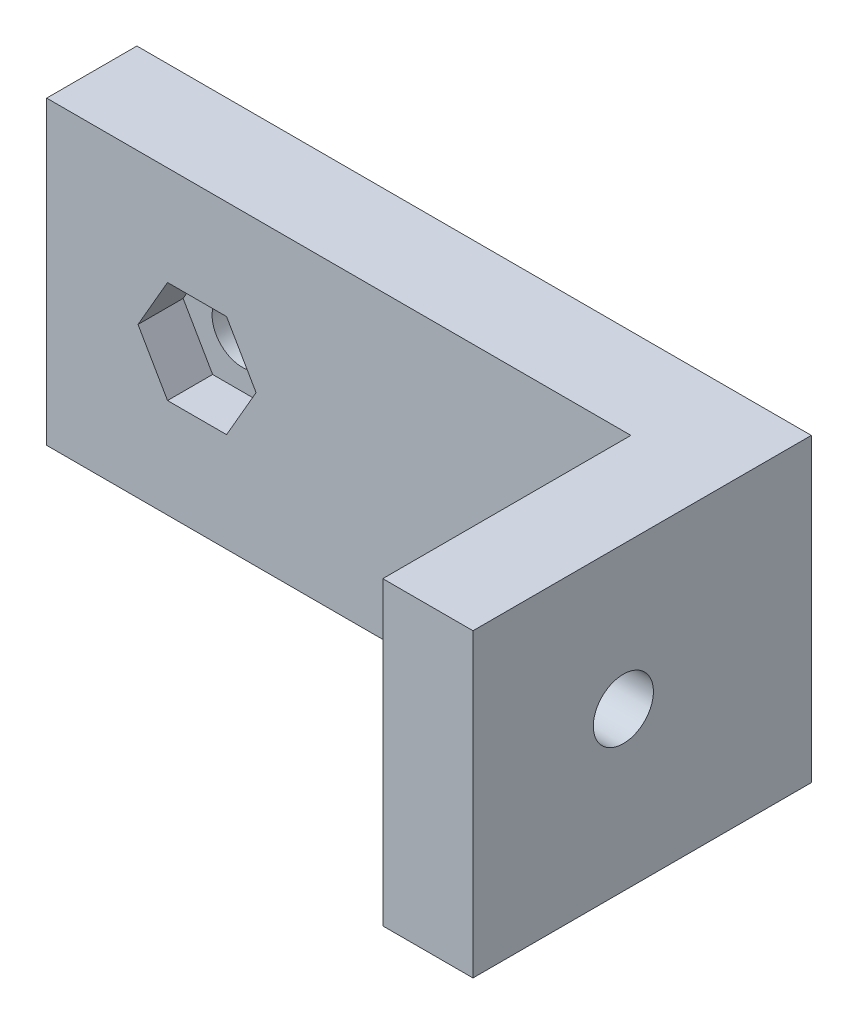
SolidWorks part; units mm, degrees
material "ABS"
ref_plane "Front Plane" through (0, 0, 0) normal (0, 0, 1) x (1, 0, 0)
ref_plane "Top Plane" through (0, 0, 0) normal (0, 1, 0) x (1, 0, 0)
ref_plane "Right Plane" through (0, 0, 0) normal (1, 0, 0) x (0, 0, -1)
sketch "Sketch1" plane through (0, 0, 0) normal (0, 0, 1) x (1, 0, 0)
  line L0 (169.7, 102.9317) -> (169.7, 86.2) construction
  line L1 (169.7, -7.5) -> (124.85, -7.5)
  line L2 (169.7, -7.5) -> (169.7, 12.5)
  line L3 (169.7, 12.5) -> (124.85, 12.5)
  line L4 (124.85, -7.5) -> (124.85, 12.5)
  line L5 (169.7, -7.5) -> (124.85, 12.5) construction
  line L6 (169.7, 12.5) -> (124.85, -7.5) construction
  line L8 (130.924, 2.5) -> (132.887, -0.9)
  line L9 (132.887, -0.9) -> (136.813, -0.9)
  line L10 (136.813, -0.9) -> (138.776, 2.5)
  line L11 (138.776, 2.5) -> (136.813, 5.9)
  line L12 (136.813, 5.9) -> (132.887, 5.9)
  line L13 (132.887, 5.9) -> (130.924, 2.5)
  circle A0 centre (134.85, 2.5) radius 2
  circle A1 centre (134.85, 2.5) radius 3.4 construction
  point P4 (147.275, 2.5)
  point P10 (134.85, 5.9)
  dimension "D2" = 10
  dimension "D3" = 10
  dimension "D4" = 10
  dimension "D1" = 6.8
extrude "Boss-Extrude1" add sketch "Sketch1" along normal blind 3 contours L4 L1 L2 L3 L13 L12 L11 L10 L9 L8 | L12 L13 L8 L9 L10 L11 A0 region at (147.8556, 2.5, 0) region at (131.9955, 4.1481, 0)
extrude "Boss-Extrude2" add sketch "Sketch1<4>" along normal blind 3 from surface contours L4 L1 L2 L3 L13 L12 L11 L10 L9 L8 region at (147.8556, 2.5, 0) starting at face at (147.275, 2.5, 3)
sketch "Sketch1<4>" plane through (0, 0, 0) normal (0, 0, 1) x (1, 0, 0) same geometry as "Sketch1"
sketch "Sketch5" plane through (169.7, 0, 0) normal (-1, 0, 0) x (0, 0, 1)
  line L0 (6, 12.5) -> (0, 12.5) construction
  line L1 (6, -7.5) -> (22.5, -7.5)
  line L2 (6, -7.5) -> (6, 12.5)
  line L3 (6, 12.5) -> (22.5, 12.5)
  line L4 (22.5, -7.5) -> (22.5, 12.5)
  line L5 (6, -7.5) -> (22.5, 12.5) construction
  line L6 (6, 12.5) -> (22.5, -7.5) construction
  line L8 (12.5, -0.926) -> (15.9, 1.037)
  line L9 (15.9, 1.037) -> (15.9, 4.963)
  line L10 (15.9, 4.963) -> (12.5, 6.926)
  line L11 (12.5, 6.926) -> (9.1, 4.963)
  line L12 (9.1, 4.963) -> (9.1, 1.037)
  line L13 (9.1, 1.037) -> (12.5, -0.926)
  circle A0 centre (12.5, 3) radius 2
  circle A1 centre (12.5, 3) radius 3.4 construction
  point P7 (14.25, 2.5)
  circle M18 centre (12.5, 3) radius 2
  dimension "D1" = 10
  dimension "D2" = 6.8
extrude "Boss-Extrude3" add sketch "Sketch5" along normal blind 3 contours L1 L4 L3 L2 L13 L12 L11 L10 L9 L8 | L12 L13 L8 L9 L10 L11 M18 region at (169.7, 2.5, 6.2593) region at (169.7, 0.1455, 10.8519)
extrude "Boss-Extrude4" add sketch "Sketch5<3>" along normal blind 3 from surface contours L1 L4 L3 L2 L13 L12 L11 L10 L9 L8 region at (169.7, 2.5, 6.2593) starting at face at (166.7, 2.5, 14.25)
sketch "Sketch5<3>" plane through (169.7, 0, 0) normal (-1, 0, 0) x (0, 0, 1) same geometry as "Sketch5"
